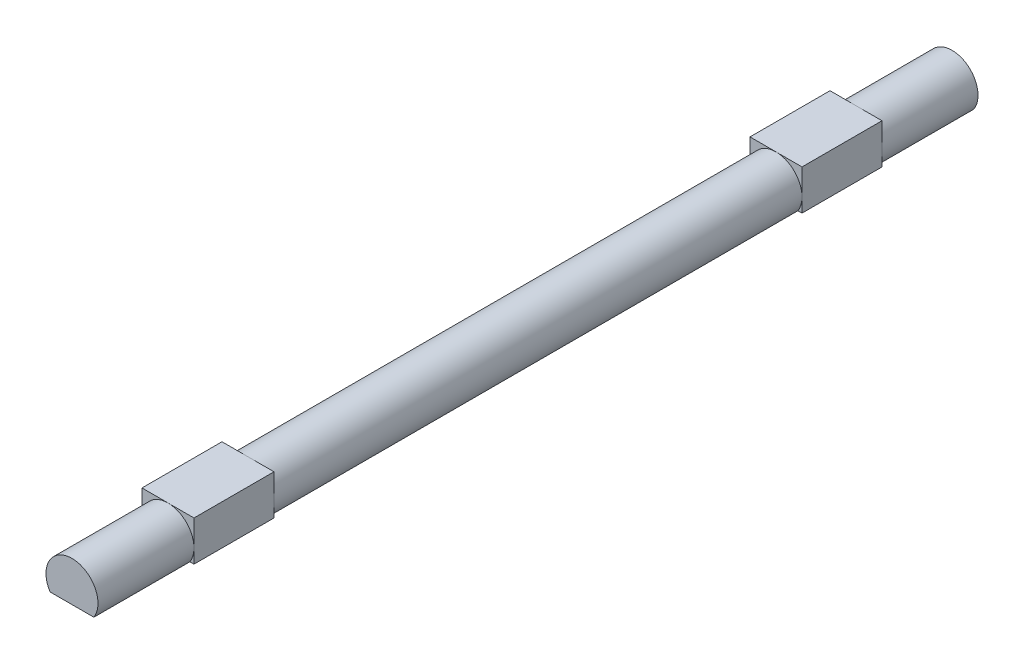
SolidWorks part; units mm, degrees
ref_plane "Front Plane" through (0, 0, 0) normal (0, 0, 1) x (1, 0, 0)
ref_plane "Top Plane" through (0, 0, 0) normal (0, 1, 0) x (1, 0, 0)
ref_plane "Right Plane" through (0, 0, 0) normal (1, 0, 0) x (0, 0, -1)
ref_plane "Plane1" through (0, 0, 43) normal (0, 0, 1) x (1, 0, 0)
sketch "Sketch2" plane through (0, 0, 0) normal (0, 0, 1) x (1, 0, 0)
  line L0 (30.9996, 3.2453) -> (25.5284, 3.2453)
  circle A1 centre (28.264, 5) radius 3.25
extrude "Boss-Extrude1" add sketch "Sketch2" along normal blind 55 and the other way blind 55 contours L0 A1 region at (28.264, 5.4978, 0)
sketch "Sketch4" plane through (0, 0, 43) normal (0, 0, 1) x (1, 0, 0)
  line L1 (31.514, 3.2453) -> (25.014, 3.2453)
  line L2 (31.514, 3.2453) -> (31.514, 8.25)
  line L3 (31.514, 8.25) -> (25.014, 8.25)
  line L4 (25.014, 3.2453) -> (25.014, 8.25)
extrude "Boss-Extrude3" add sketch "Sketch4" against normal blind 10
mirror "Mirror1" about plane through (0, 0, 0) normal (0, 0, 1) of "Boss-Extrude3"
